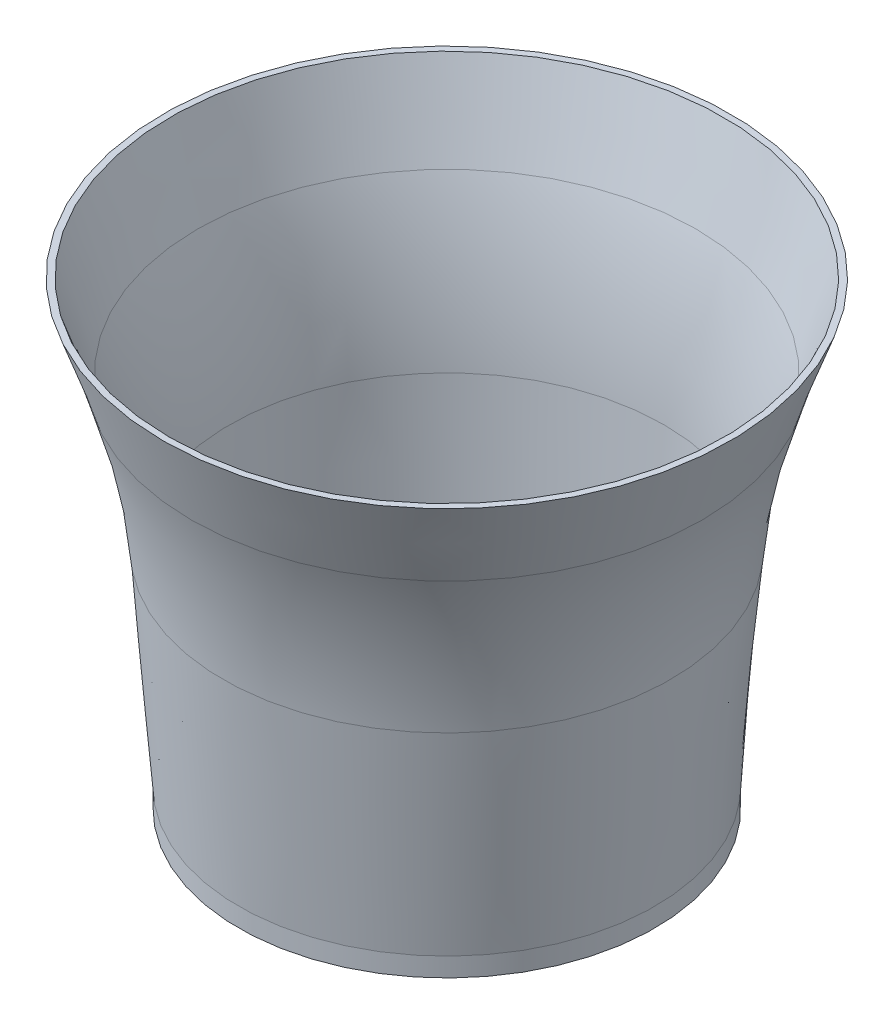
SolidWorks part; units mm, degrees
ref_plane "Front Plane" through (0, 0, 0) normal (0, 0, 1) x (1, 0, 0)
ref_plane "Top Plane" through (0, 0, 0) normal (0, 1, 0) x (1, 0, 0)
ref_plane "Right Plane" through (0, 0, 0) normal (1, 0, 0) x (0, 0, -1)
sketch "Sketch1" plane through (0, 0, 0) normal (0, 0, 1) x (1, 0, 0)
  line L0 (0, 0) -> (0, 81.659)
sketch "Sketch2" plane through (0, 0, 0) normal (1, 0, 0) x (0, 0, -1)
  line L0 (-32, 0) -> (-33, 0)
  line L1 (-33, 0) -> (-36.5, 45)
  line L2 (-36.5, 45) -> (-35.5, 45)
  line L3 (-35.5, 45) -> (-32, 0)
  line L4 (-32, 0) -> (-12.3281, 0) construction
  line L5 (0, 0) -> (0, 81.659) construction
  dimension "D1" = 32
  dimension "D2" = 1
  dimension "D3" = 35.5
  dimension "D4" = 45
revolve "Revolve1" add sketch "Sketch2" angle 360 about L0
sketch "Sketch4" plane through (0, 0, 0) normal (0, -1, 0) x (1, 0, 0)
  line L0 (0, 0) -> (0, 17) construction
  line L1 (0, 32) -> (0, 37.2156) construction
  circle A8 centre (0, 10) radius 2
  circle A9 centre (0, -5) radius 2
  circle A10 centre (0, 0) radius 33
  point P21 (0, 0)
  dimension "D4" = 4
  dimension "D5" = 4
  dimension "D6" = 5
  dimension "D7" = 10
extrude "Boss-Extrude1" add sketch "Sketch4" along normal blind 3
ref_plane "Plane1" through (0, 45, 0) normal (0, 1, 0) x (1, 0, 0)
ref_plane "Plane2" through (0, 70, 0) normal (0, 1, 0) x (1, 0, 0)
sketch "Sketch8" plane through (0, 45, 0) normal (0, 1, 0) x (1, 0, 0)
  circle A0 centre (0, 0) radius 35.5
  circle A1 centre (0, 0) radius 36.5
  dimension "D1" = 71
  dimension "D2" = 73
sketch "Sketch9" plane through (0, 70, 0) normal (0, 1, 0) x (1, 0, 0)
  circle A0 centre (0, 0) radius 44
  circle A1 centre (0, 0) radius 45
  dimension "D1" = 88
  dimension "D2" = 90
loft "Loft1" add section "Sketch8" section "Sketch9" connector at (-32.6765, 45, -16.2634) connector at (-40.3863, 70, -19.848)
loft "Cut-Loft1" cut section "Sketch8<3>" section "Sketch9<3>" connector at (-28.5752, 45, -21.0644) connector at (-35.8426, 70, -25.5207)
sketch "Sketch8<3>" plane through (0, 45, 0) normal (0, 1, 0) x (1, 0, 0) same geometry as "Sketch8"
sketch "Sketch9<3>" plane through (0, 70, 0) normal (0, 1, 0) x (1, 0, 0) same geometry as "Sketch9"
fillet "Fillet1" radius 100 1 edges at (0, 45, 35.5)
fillet "Fillet2" radius 100 1 edges at (0, 45, 36.5)
sketch "Sketch10" plane through (0, 0, 0) normal (0, 1, 0) x (1, 0, 0)
  circle A0 centre (0, 0) radius 27.5
  circle A1 centre (0, 5) radius 2
  circle A2 centre (0, -10) radius 2
  dimension "D1" = 55
extrude "Boss-Extrude2" add sketch "Sketch10" along normal blind 5 from surface starting at face at (0, 0, -7)
sketch "Sketch11" plane through (0, 0, 0) normal (0, 1, 0) x (1, 0, 0)
  line L0 (0, 0) -> (0, 32) construction
  circle A0 centre (0, 0) radius 32 construction
  circle A1 centre (0, 29.6591) radius 2.3409
  circle A2 centre (29.6591, 0) radius 2.3409
  circle A3 centre (0, -29.6591) radius 2.3409
  circle A4 centre (-29.6591, 0) radius 2.3409
  point P16 (0, 0)
  dimension "D1" = 4
extrude "Cut-Extrude1" cut sketch "Sketch11" against normal through all both and the other way through all
sketch "Sketch12" plane through (0, 5, 0) normal (0, 1, 0) x (1, 0, 0)
  circle A0 centre (0, 5) radius 4
  circle A1 centre (0, -10) radius 4
  dimension "D1" = 8
  dimension "D2" = 8
extrude "Cut-Extrude2" cut sketch "Sketch12" against normal blind 3
